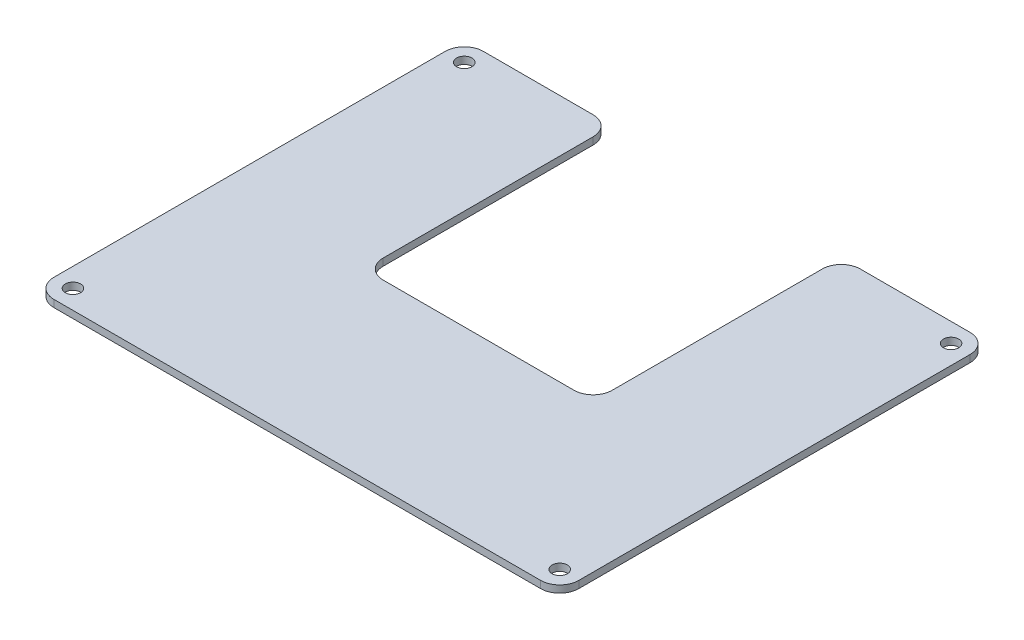
SolidWorks part; units mm, degrees
ref_plane "Front Plane" through (0, 0, 0) normal (0, 0, 1) x (1, 0, 0)
ref_plane "Top Plane" through (0, 0, 0) normal (0, 1, 0) x (1, 0, 0)
ref_plane "Right Plane" through (0, 0, 0) normal (1, 0, 0) x (0, 0, -1)
sketch "Sketch1" plane through (0, 0, 0) normal (0, 1, 0) x (1, 0, 0)
  line L1 (-55, -45) -> (55, -45)
  line L2 (-55, -45) -> (-55, 45)
  line L3 (-55, 45) -> (55, 45)
  line L4 (55, -45) -> (55, 45)
  line L5 (-55, -45) -> (55, 45) construction
  line L6 (-55, 45) -> (55, -45) construction
  point P0 (0, 0)
extrude "Boss-Extrude1" add sketch "Sketch1" along normal blind 1.5
sketch "Sketch2" plane through (0, 0, 0) normal (0, -1, 0) x (-1, 0, 0)
  line L0 (0, 45) -> (-24, 45)
  line L1 (-55, 45) -> (55, 45) construction
  line L2 (-24, 45) -> (-24, -7)
  line L3 (0, 45) -> (24, 45)
  line L4 (24, 45) -> (24, -7)
  line L5 (24, -7) -> (-24, -7)
extrude "Cut-Extrude1" cut sketch "Sketch2" against normal blind 10
fillet "Fillet1" radius 4 8 edges at (55, 0.75, -45) (-55, 0.75, -45) (55, 0.75, 45) (-55, 0.75, 45) (24, 0.75, 7) (-24, 0.75, 7) (-24, 0.75, -45) (24, 0.75, -45)
sketch "Sketch4" plane through (0, 0, 0) normal (0, -1, 0) x (-1, 0, 0)
  circle A0 centre (51, -41) radius 1.6
  circle A1 centre (51, 41) radius 1.6
  circle A2 centre (-51, 41) radius 1.6
  circle A3 centre (-51, -41) radius 1.6
extrude "Cut-Extrude2" cut sketch "Sketch4" against normal blind 10
